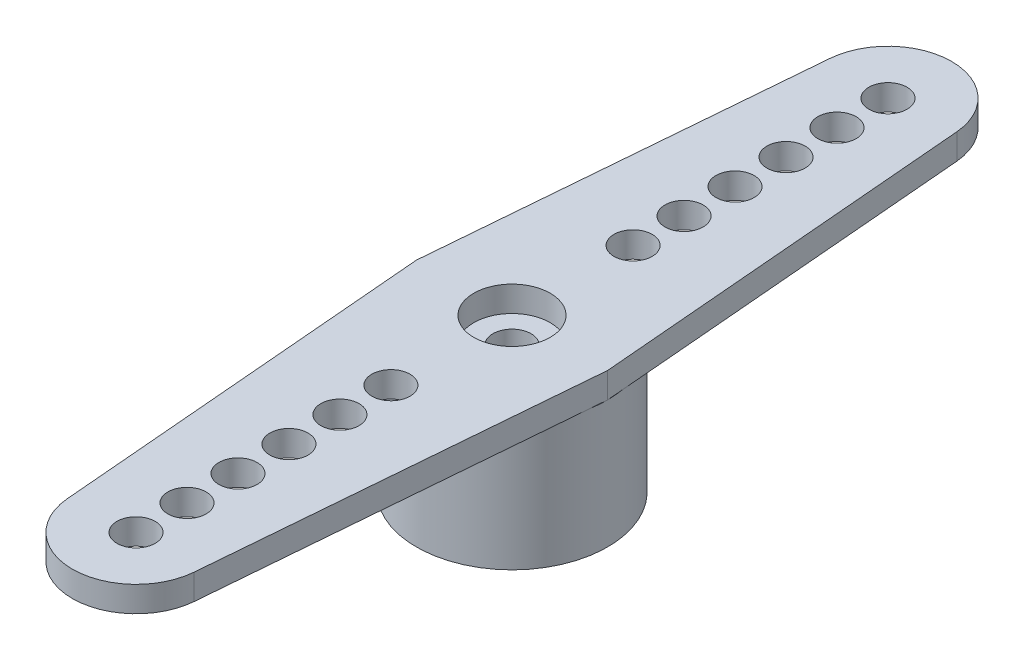
SolidWorks part; units mm, degrees
ref_plane "Front Plane" through (0, 0, 0) normal (0, 0, 1) x (1, 0, 0)
ref_plane "Top Plane" through (0, 0, 0) normal (0, 1, 0) x (1, 0, 0)
ref_plane "Right Plane" through (0, 0, 0) normal (1, 0, 0) x (0, 0, -1)
sketch "Sketch1" plane through (0, 0, 0) normal (0, 1, 0) x (1, 0, 0)
  line L0 (0, -14.75) -> (0, 14.75) construction
  line L1 (-2.5, -14.75) -> (-2.5, 14.75) construction
  line L2 (2.5, -14.75) -> (2.5, 14.75) construction
  line L3 (-2.4912, 14.9596) -> (-3.75, 0)
  line L4 (-3.75, 0) -> (-2.4912, -14.9596)
  line L5 (0, 31.3405) -> (0, -28.9858) construction
  line L6 (2.4912, 14.9596) -> (3.75, 0)
  line L7 (3.75, 0) -> (2.4912, -14.9596)
  line L8 (0, 0) -> (13.4273, 0) construction
  arc A0 (-2.5, -14.75) -> (2.5, -14.75) centre (0, -14.75) ccw construction
  arc A1 (2.5, 14.75) -> (-2.5, 14.75) centre (0, 14.75) ccw construction
  arc A2 (-2.4912, 14.9596) -> (2.4912, 14.9596) centre (0, 14.75) cw
  arc A3 (-2.4912, -14.9596) -> (2.4912, -14.9596) centre (0, -14.75) ccw
  circle A4 centre (0, 14.75) radius 0.75
  circle A5 centre (0, 12.75) radius 0.75
  circle A6 centre (0, 10.75) radius 0.75
  circle A7 centre (0, 8.75) radius 0.75
  circle A8 centre (0, 6.75) radius 0.75
  circle A9 centre (0, 4.75) radius 0.75
  circle A10 centre (0, 0) radius 3.75 construction
  circle A11 centre (0, 0) radius 0.75
  circle A12 centre (0, -14.75) radius 0.75
  circle A13 centre (0, -12.75) radius 0.75
  circle A14 centre (0, -10.75) radius 0.75
  circle A15 centre (0, -8.75) radius 0.75
  circle A16 centre (0, -6.75) radius 0.75
  circle A17 centre (0, -4.75) radius 0.75
  point P2 (0, 0)
  dimension "D1" = 2.5
  dimension "D4" = 1.5
  dimension "D2" = 29.5
  dimension "D3" = 3.75
  dimension "D6" = 2
  dimension "D5" = 6
extrude "Boss-Extrude1" add sketch "Sketch1" along normal blind 1
sketch "Sketch3" plane through (0, 0, 0) normal (0, -1, 0) x (1, 0, 0)
  circle A0 centre (0, 0) radius 3.75 construction
  circle A1 centre (0, 0) radius 3.75
  circle A2 centre (0, 0) radius 1.5
  dimension "D1" = 3
extrude "Boss-Extrude2" add sketch "Sketch3" along normal blind 5 contours A1
extrude "Cut-Extrude1" cut sketch "Sketch3<3>" against normal through all contours A2
sketch "Sketch3<3>" plane through (0, 0, 0) normal (0, -1, 0) x (1, 0, 0) same geometry as "Sketch3"
extrude "Cut-Extrude2" cut sketch "Sketch1<2>" against normal through all contours A11
sketch "Sketch1<2>" plane through (0, 0, 0) normal (0, 1, 0) x (1, 0, 0) same geometry as "Sketch1"
sketch "Sketch4" plane through (0, -5, 0) normal (0, -1, 0) x (1, 0, 0)
  line L0 (0, 14.75) -> (0, -14.75) construction
  circle A0 centre (0, 0) radius 2.355
  dimension "D1" = 4.71
extrude "Cut-Extrude3" cut sketch "Sketch4" against normal blind 2
sketch "Sketch5" plane through (0, -5, 0) normal (0, -1, 0) x (1, 0, 0)
  line L0 (-0.1414, 2.3507) -> (0, 2.4922)
  line L1 (0, 14.75) -> (0, -14.75) construction
  line L2 (0, 2.4922) -> (0.1414, 2.3507)
  circle A0 centre (0, 0) radius 2.355 construction
  arc A1 (0.1414, 2.3507) -> (-0.1414, 2.3507) centre (0, 0) ccw
  circle A2 centre (0, 0) radius 2.355 construction
  point P7 (-0.1458, 2.3505)
  dimension "D1" = 0.2
extrude "Cut-Extrude4" cut sketch "Sketch5" against normal up to surface (2 mm away) up to face at (0, -3, -2.355)
pattern_circular "CirPattern1" count 56 over 360 about axis through (0, -3, 0) along (0, -1, 0) of "Cut-Extrude4" reverse direction yes
